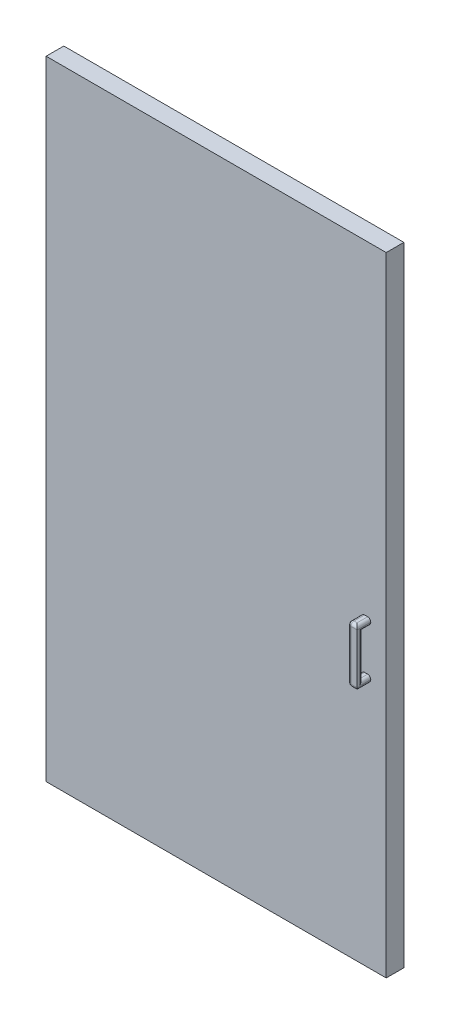
SolidWorks part; units mm, degrees
ref_plane "Front Plane" through (0, 0, 0) normal (0, 0, 1) x (1, 0, 0)
ref_plane "Top Plane" through (0, 0, 0) normal (0, 1, 0) x (1, 0, 0)
ref_plane "Right Plane" through (0, 0, 0) normal (1, 0, 0) x (0, 0, -1)
sketch "Sketch1" plane through (0, 0, 0) normal (0, 0, 1) x (1, 0, 0)
  line L0 (0, 0) -> (0, 18.7953) construction
  line L1 (0, 0) -> (0, 446.2018)
  line L2 (0, 446.2018) -> (-1100, 446.2018)
  line L3 (-1100, 446.2018) -> (-1100, -1585.7982)
  line L4 (-1100, -1585.7982) -> (0, -1585.7982)
  line L5 (0, -1585.7982) -> (0, 0)
  line L7 (-130, -553.7982) -> (-100, -553.7982)
  line L8 (-130, -553.7982) -> (-130, -735.7982)
  line L9 (-130, -735.7982) -> (-100, -735.7982)
  line L10 (-100, -553.7982) -> (-100, -735.7982)
  line L11 (-130, -553.7982) -> (-100, -735.7982) construction
  line L12 (-130, -735.7982) -> (-100, -553.7982) construction
  point P9 (-115, -644.7982)
  dimension "D1" = 1100
  dimension "D2" = 2032
  dimension "D3" = 30
  dimension "D4" = 182
  dimension "D5" = 850
  dimension "D6" = 100
extrude "Boss-Extrude2" add sketch "Sketch1" along normal blind 57.15 contours L3 L4 L5 L1 L2
sketch "Sketch4" plane through (0, 0, 57.15) normal (0, 0, 1) x (1, 0, 0)
  line L0 (-50, 0) -> (-50, -1857.8255) construction
  line L1 (-1100, -1585.7982) -> (0, -1585.7982) construction
  line L2 (-80, -603.7982) -> (-50, -603.7982)
  line L3 (-80, -603.7982) -> (-80, -785.7982)
  line L4 (-80, -785.7982) -> (-50, -785.7982)
  line L5 (-50, -603.7982) -> (-50, -785.7982)
  line L6 (-80, -603.7982) -> (-50, -785.7982) construction
  line L7 (-80, -785.7982) -> (-50, -603.7982) construction
  point P1 (-65, -694.7982)
  dimension "D1" = 50
  dimension "D2" = 30
  dimension "D3" = 182
  dimension "D4" = 800
extrude "Boss-Extrude3" add sketch "Sketch4" along normal blind 44
sketch "Sketch5" plane through (-80, 0, 0) normal (-1, 0, 0) x (0, 0, 1)
  line L0 (57.15, -603.7982) -> (57.15, -785.7982)
  line L1 (57.15, -624.7982) -> (83.15, -624.7982)
  line L2 (83.15, -624.7982) -> (83.15, -764.7982)
  line L3 (83.15, -764.7982) -> (57.15, -764.7982)
  line L4 (57.15, -624.7982) -> (57.15, -764.7982)
  line L5 (101.15, -785.7982) -> (57.15, -785.7982) construction
  dimension "D1" = 140
  dimension "D2" = 21
  dimension "D3" = 26
extrude "Cut-Extrude1" cut sketch "Sketch5" against normal blind 44 contours L3 L2 L1 L0 region at (-80, -694.7982, 70.15)
fillet "Fillet1" radius 10 13 edges at (-80, -694.7982, 83.15) (-80, -603.7982, 79.15) (-80, -624.7982, 70.15) (-50, -603.7982, 79.15) (-50, -624.7982, 70.15) (-50, -694.7982, 83.15) (-50, -764.7982, 70.15) (-50, -785.7982, 79.15) (-80, -785.7982, 79.15) (-80, -764.7982, 70.15) (-80, -694.7982, 101.15) (-65, -785.7982, 101.15) (-65, -603.7982, 101.15)
sketch "Sketch6" plane through (0, 0, 0) normal (0, 0, -1) x (-1, 0, 0)
  line L1 (35, -272.0487) -> (165, -272.0487)
  line L2 (35, -272.0487) -> (35, -812.0487)
  line L3 (35, -812.0487) -> (165, -812.0487)
  line L4 (165, -272.0487) -> (165, -812.0487)
  line L5 (0, -1585.7982) -> (0, 446.2018) construction
  point P4 (100, -812.0487)
  dimension "D1" = 100
  dimension "D2" = 130
  dimension "D3" = 540
extrude "Boss-Extrude4" add sketch "Sketch6" along normal blind 10
